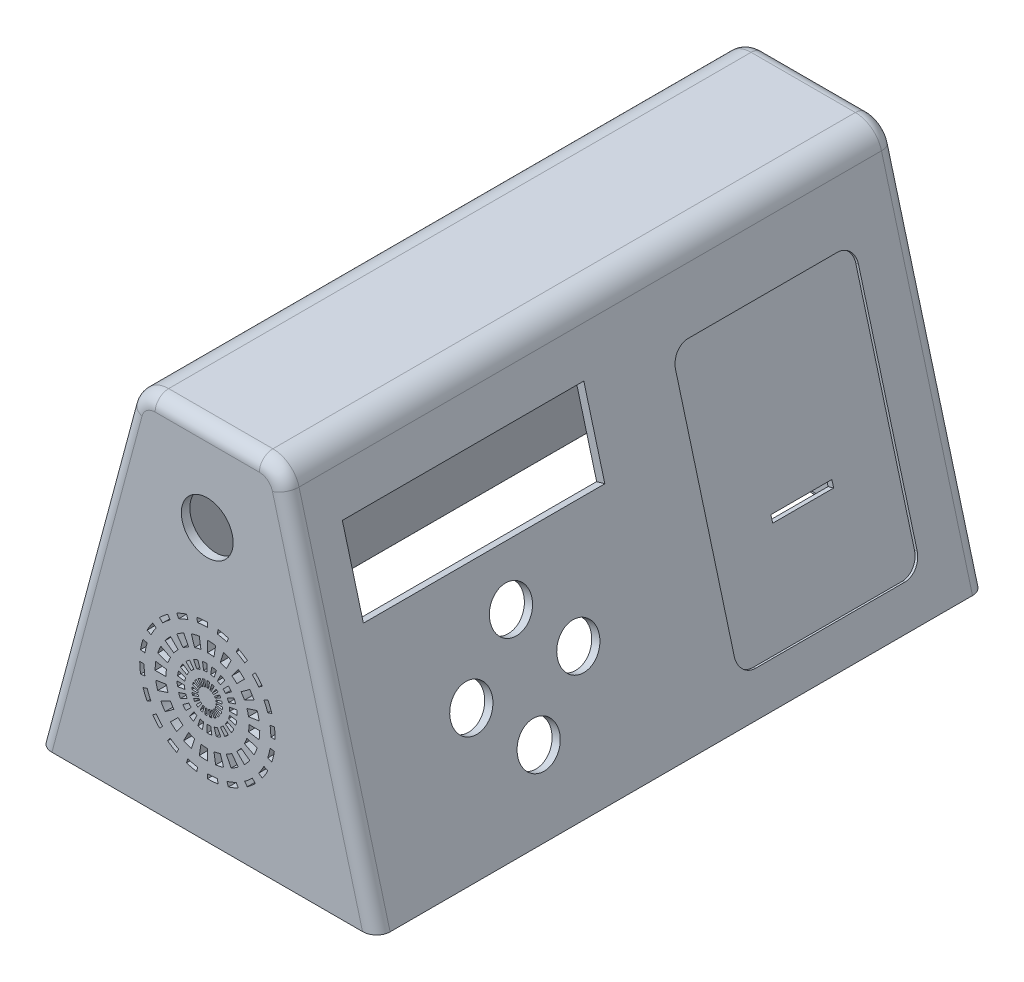
SolidWorks part; units mm, degrees
ref_plane "Front Plane" through (0, 0, 0) normal (0, 0, 1) x (1, 0, 0)
ref_plane "Top Plane" through (0, 0, 0) normal (0, 1, 0) x (1, 0, 0)
ref_plane "Right Plane" through (0, 0, 0) normal (1, 0, 0) x (0, 0, -1)
sketch "Sketch1" plane through (0, 0, 0) normal (0, 0, 1) x (1, 0, 0)
  line L0 (-50, 0) -> (50, 0)
  line L1 (-50, 0) -> (-21.5299, 106.2518)
  line L2 (50, 0) -> (21.5299, 106.2518)
  line L3 (-21.5299, 106.2518) -> (21.5299, 106.2518)
  point P3 (0, 0)
  dimension "D1" = 75
  dimension "D2" = 110
  dimension "D3" = 75
  dimension "D4" = 110
extrude "Boss-Extrude1" add sketch "Sketch1" along normal mid plane 180
shell "Shell1" thickness 2.5
sketch "Sketch2" plane through (46.6506, 12.5, 0) normal (0.9659, 0.2588, 0) x (0, 0, -1)
  line L1 (-76.3694, 78.7405) -> (-5.0694, 78.7405)
  line L2 (-76.3694, 78.7405) -> (-76.3694, 54.7405)
  line L3 (-76.3694, 54.7405) -> (-5.0694, 54.7405)
  line L4 (-5.0694, 78.7405) -> (-5.0694, 54.7405)
  dimension "D1" = 71.3
  dimension "D2" = 24
extrude "Cut-Extrude1" cut sketch "Sketch2" against normal up to next contours L2 L1 L4 L3
sketch "Sketch3" plane through (46.6506, 12.5, 0) normal (0.9659, 0.2588, 0) x (0, 0, -1)
  line L1 (24.7907, 75.0481) -> (68.7907, 75.0481)
  line L2 (19.7907, 70.0481) -> (19.7907, 3.0481)
  line L3 (24.7907, -1.9519) -> (68.7907, -1.9519)
  line L4 (73.7907, 70.0481) -> (73.7907, 3.0481)
  arc A0 (68.7907, 75.0481) -> (73.7907, 70.0481) centre (68.7907, 70.0481) cw
  arc A1 (24.7907, 75.0481) -> (19.7907, 70.0481) centre (24.7907, 70.0481) ccw
  arc A2 (68.7907, -1.9519) -> (73.7907, 3.0481) centre (68.7907, 3.0481) ccw
  arc A3 (19.7907, 3.0481) -> (24.7907, -1.9519) centre (24.7907, 3.0481) ccw
  point P6 (73.7907, 75.0481)
  point P9 (19.7907, 75.0481)
  point P12 (73.7907, -1.9519)
  dimension "D3" = 5
  dimension "D4" = 5
  dimension "D5" = 5
  dimension "D6" = 5
  dimension "D1" = 54
  dimension "D2" = 77
extrude "Cut-Extrude2" cut sketch "Sketch3" against normal blind 0.81 contours L2 A3 L3 A2 L4 A0 L1 A1
sketch "Sketch4" plane through (45.8682, 12.2904, 0) normal (0.9659, 0.2588, 0) x (0, 0, -1)
  line L0 (24.7907, -1.9519) -> (68.7907, -1.9519) construction
  line L1 (37.7907, 27.8007) -> (55.7907, 27.8007)
  line L2 (37.7907, 27.8007) -> (37.7907, 25.8007)
  line L3 (37.7907, 25.8007) -> (55.7907, 25.8007)
  line L4 (55.7907, 27.8007) -> (55.7907, 25.8007)
  point P4 (46.7907, 25.8007)
  point P7 (46.7907, -1.9519)
  dimension "D1" = 18
  dimension "D2" = 2
extrude "Cut-Extrude3" cut sketch "Sketch4" against normal up to next
sketch "Sketch5" plane through (0, 0, 0) normal (0, -1, 0) x (1, 0, 0)
  line L7 (-48.5, 88.5) -> (48.5, 88.5)
  line L8 (-48.5, 88.5) -> (-48.5, -88.5)
  line L9 (-48.5, -88.5) -> (48.5, -88.5)
  line L10 (48.5, 88.5) -> (48.5, -88.5)
extrude "Cut-Extrude4" cut sketch "Sketch5" against normal blind 1.5
sketch "Sketch6" plane through (46.6506, 12.5, 0) normal (0.9659, 0.2588, 0) x (0, 0, -1)
  circle A0 centre (-36.6513, 24.0152) radius 15.8 construction
  circle A1 centre (-36.6513, 39.8152) radius 6.175
  circle A2 centre (-20.8513, 24.0152) radius 6.175
  circle A3 centre (-36.6513, 8.2152) radius 6.175
  circle A4 centre (-52.4513, 24.0152) radius 6.175
extrude "Cut-Extrude5" cut sketch "Sketch6" against normal up to next
sketch "Sketch7" plane through (0, 0, 90) normal (0, 0, 1) x (1, 0, 0)
  line L0 (-19.9366, 36.1957) -> (20.0634, 36.1957)
  line L1 (-19.6904, 39.3244) -> (19.8171, 33.067)
  line L2 (-18.9578, 42.376) -> (19.0845, 30.0153)
  line L3 (-17.7568, 45.2755) -> (17.8835, 27.1159)
  line L4 (-16.117, 47.9514) -> (16.2437, 24.44)
  line L5 (-14.0788, 50.3378) -> (14.2055, 22.0535)
  line L6 (-11.6923, 52.376) -> (11.8191, 20.0153)
  line L7 (-9.0164, 54.0158) -> (9.1432, 18.3755)
  line L8 (-6.117, 55.2168) -> (6.2437, 17.1745)
  line L9 (-3.0653, 55.9494) -> (3.1921, 16.4419)
  line L10 (0.0634, 56.1957) -> (0.0634, 16.1957)
  line L11 (3.1921, 55.9494) -> (-3.0653, 16.4419)
  line L12 (6.2437, 55.2168) -> (-6.117, 17.1745)
  line L13 (9.1432, 54.0158) -> (-9.0164, 18.3755)
  line L14 (11.8191, 52.376) -> (-11.6923, 20.0153)
  line L15 (14.2055, 50.3378) -> (-14.0788, 22.0535)
  line L16 (16.2437, 47.9514) -> (-16.117, 24.44)
  line L17 (17.8835, 45.2755) -> (-17.7568, 27.1159)
  line L18 (19.0845, 42.376) -> (-18.9578, 30.0153)
  line L19 (19.8171, 39.3244) -> (-19.6904, 33.067)
  line L20 (20.0634, 36.1957) -> (-19.9366, 36.1957)
  line L21 (19.8171, 33.067) -> (-19.6904, 39.3244)
  line L22 (19.0845, 30.0153) -> (-18.9578, 42.376)
  line L23 (17.8835, 27.1159) -> (-17.7568, 45.2755)
  line L24 (16.2437, 24.44) -> (-16.117, 47.9514)
  line L25 (14.2055, 22.0535) -> (-14.0788, 50.3378)
  line L26 (11.8191, 20.0153) -> (-11.6923, 52.376)
  line L27 (9.1432, 18.3755) -> (-9.0164, 54.0158)
  line L28 (6.2437, 17.1745) -> (-6.117, 55.2168)
  line L29 (3.1921, 16.4419) -> (-3.0653, 55.9494)
  line L30 (0.0634, 16.1957) -> (0.0634, 56.1957)
  line L31 (-3.0653, 16.4419) -> (3.1921, 55.9494)
  line L32 (-6.117, 17.1745) -> (6.2437, 55.2168)
  line L33 (-9.0164, 18.3755) -> (9.1432, 54.0158)
  line L34 (-11.6923, 20.0153) -> (11.8191, 52.376)
  line L35 (-14.0788, 22.0535) -> (14.2055, 50.3378)
  line L36 (-16.117, 24.44) -> (16.2437, 47.9514)
  line L37 (-17.7568, 27.1159) -> (17.8835, 45.2755)
  line L38 (-18.9578, 30.0153) -> (19.0845, 42.376)
  line L39 (-19.6904, 33.067) -> (19.8171, 39.3244)
  circle A0 centre (0.0634, 36.1957) radius 20
  circle A1 centre (0.0634, 36.1957) radius 18.7138
  circle A2 centre (0.0634, 36.1957) radius 15.4462
  circle A3 centre (0.0634, 36.1957) radius 12.2664
  circle A4 centre (0.0634, 36.1957) radius 9.4693
  circle A5 centre (0.0634, 36.1957) radius 6.7104
  circle A6 centre (0.0634, 36.1957) radius 4.4019
  circle A7 centre (0.0634, 36.1957) radius 2.8126
  circle A8 centre (0.0634, 36.1957) radius 1.3333
  point P93 (0.0634, 36.1957)
  dimension "D1" = 40
extrude "Cut-Extrude6" cut sketch "Sketch7" against normal blind 2.54
sketch "Sketch8" plane through (0, 0, 90) normal (0, 0, 1) x (1, 0, 0)
  line L0 (-8.8943, 36.7332) -> (8.8342, 36.7332)
  line L1 (-8.7851, 38.1198) -> (8.7251, 35.3465)
  line L2 (-8.4604, 39.4724) -> (8.4004, 33.994)
  line L3 (-7.9281, 40.7574) -> (7.8681, 32.7089)
  line L4 (-7.2013, 41.9434) -> (7.1413, 31.5229)
  line L5 (-6.298, 43.0011) -> (6.2379, 30.4652)
  line L6 (-5.2403, 43.9045) -> (5.1802, 29.5619)
  line L7 (-4.0543, 44.6312) -> (3.9942, 28.8351)
  line L8 (-2.7692, 45.1635) -> (2.7092, 28.3028)
  line L9 (-1.4167, 45.4883) -> (1.3566, 27.9781)
  line L10 (-0.03, 45.5974) -> (-0.03, 27.8689)
  line L11 (1.3566, 45.4883) -> (-1.4167, 27.9781)
  line L12 (2.7092, 45.1635) -> (-2.7692, 28.3028)
  line L13 (3.9942, 44.6312) -> (-4.0543, 28.8351)
  line L14 (5.1802, 43.9045) -> (-5.2403, 29.5619)
  line L15 (6.2379, 43.0011) -> (-6.298, 30.4652)
  line L16 (7.1413, 41.9434) -> (-7.2013, 31.5229)
  line L17 (7.8681, 40.7574) -> (-7.9281, 32.7089)
  line L18 (8.4004, 39.4724) -> (-8.4604, 33.994)
  line L19 (8.7251, 38.1198) -> (-8.7851, 35.3465)
  line L20 (8.8342, 36.7332) -> (-8.8943, 36.7332)
  line L21 (8.7251, 35.3465) -> (-8.7851, 38.1198)
  line L22 (8.4004, 33.994) -> (-8.4604, 39.4724)
  line L23 (7.8681, 32.7089) -> (-7.9281, 40.7574)
  line L24 (7.1413, 31.5229) -> (-7.2013, 41.9434)
  line L25 (6.2379, 30.4652) -> (-6.298, 43.0011)
  line L26 (5.1802, 29.5619) -> (-5.2403, 43.9045)
  line L27 (3.9942, 28.8351) -> (-4.0543, 44.6312)
  line L28 (2.7092, 28.3028) -> (-2.7692, 45.1635)
  line L29 (1.3566, 27.9781) -> (-1.4167, 45.4883)
  line L30 (-0.03, 27.8689) -> (-0.03, 45.5974)
  line L31 (-1.4167, 27.9781) -> (1.3566, 45.4883)
  line L32 (-2.7692, 28.3028) -> (2.7092, 45.1635)
  line L33 (-4.0543, 28.8351) -> (3.9942, 44.6312)
  line L34 (-5.2403, 29.5619) -> (5.1802, 43.9045)
  line L35 (-6.298, 30.4652) -> (6.2379, 43.0011)
  line L36 (-7.2013, 31.5229) -> (7.1413, 41.9434)
  line L37 (-7.9281, 32.7089) -> (7.8681, 40.7574)
  line L38 (-8.4604, 33.994) -> (8.4004, 39.4724)
  line L39 (-8.7851, 35.3465) -> (8.7251, 38.1198)
  circle A0 centre (-0.03, 36.7332) radius 8.8642
  circle A1 centre (-0.03, 36.7332) radius 6.6679
  circle A2 centre (-0.03, 36.7332) radius 4.5332
  circle A3 centre (-0.03, 36.7332) radius 2.6666
  point P88 (-0.03, 36.7332)
  dimension "D1" = 40
extrude "Cut-Extrude7" cut sketch "Sketch8" against normal blind 2.54
sketch "Sketch14" plane through (0, 0, 87.5) normal (0, 0, -1) x (-1, 0, 0)
  circle A0 centre (0.03, 36.7332) radius 20
  circle A1 centre (0.03, 36.7332) radius 19.5
  point P0 (0.03, 36.7332)
extrude "Boss-Extrude2" add sketch "Sketch14" along normal blind 3
fillet "Fillet1" radius 4 6 edges at (-35.765, 53.1259, -90) (0, 106.2518, -90) (35.765, 53.1259, -90) (35.765, 53.1259, 90) (0, 106.2518, 90) (-35.765, 53.1259, 90)
fillet "Fillet2" radius 8 6 edges at (20.6309, 105.0803, -88.8284) (20.6309, 105.0803, 88.8284) (-20.6309, 105.0803, -88.8284) (-20.6309, 105.0803, 88.8284) (-21.5299, 106.2518, 0) (21.5299, 106.2518, 0)
sketch "Sketch18" plane through (0, 0, 90) normal (0, 0, 1) x (1, 0, 0)
  circle A0 centre (0, 80.3702) radius 7.65
extrude "Cut-Extrude8" cut sketch "Sketch18" against normal blind 10
sketch "Sketch19" plane through (0, 0, -90) normal (0, 0, -1) x (-1, 0, 0)
  line L0 (-28.9389, 21.9612) -> (-19.5279, 21.9612)
  line L1 (-28.9389, 4.5407) -> (-19.5279, 4.5407)
  circle A2 centre (-24.2334, 13.2509) radius 9.9
  point P4 (-24.2334, 4.5407)
  point P5 (-24.2334, 21.9612)
extrude "Cut-Extrude9" cut sketch "Sketch19" against normal blind 10 contours L0 A2 L1
